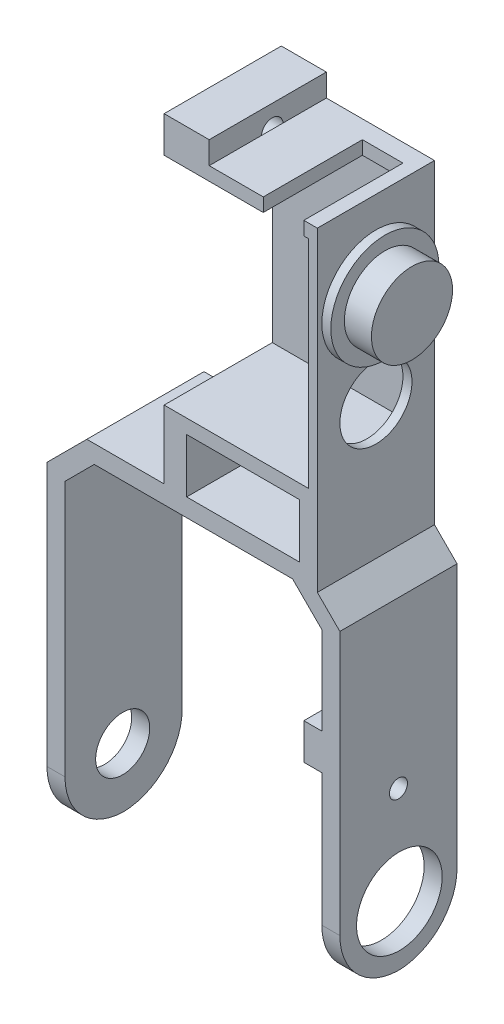
SolidWorks part; units mm, degrees
material "Plain Carbon Steel"
ref_plane "Front Plane" through (0, 0, 0) normal (0, 0, 1) x (1, 0, 0)
ref_plane "Top Plane" through (0, 0, 0) normal (0, 1, 0) x (1, 0, 0)
ref_plane "Right Plane" through (0, 0, 0) normal (1, 0, 0) x (0, 0, -1)
sketch "Sketch1" plane through (0, 0, 0) normal (0, 0, 1) x (1, 0, 0)
  line L0 (0, 20.5639) -> (0, -27.6744) construction
  line L1 (-59.1421, 0) -> (59.1421, 0)
  line L2 (59.1421, 0) -> (81.25, -22.1079)
  line L3 (81.25, -22.1079) -> (81.25, -201.25)
  line L4 (81.25, -201.25) -> (71.25, -201.25)
  line L5 (71.25, -201.25) -> (71.25, -26.25)
  line L6 (71.25, -26.25) -> (55, -10)
  line L8 (-59.1421, 0) -> (-81.25, -22.1079)
  line L9 (-81.25, -22.1079) -> (-81.25, -201.25)
  line L10 (-81.25, -201.25) -> (-71.25, -201.25)
  line L12 (55, -10) -> (-55, -10)
  line L13 (-55, -10) -> (-71.25, -26.25)
  line L14 (-71.25, -26.25) -> (-71.25, -201.25)
  point P6 (0, 0)
  point P19 (-63.125, -18.125)
  dimension "D1" = 175
  dimension "D2" = 71.25
  dimension "D3" = 10
  dimension "D4" = 10
  dimension "D5" = 10
  dimension "D6" = 135
  dimension "D7" = 55
extrude "Boss-Extrude1" add sketch "Sketch1" along normal blind 65
sketch "Sketch2" plane through (0, 0, 0) normal (0, 0, 1) x (1, 0, 0)
  line L0 (68.75, -9.6079) -> (68.75, 165.3921)
  line L1 (81.25, -22.1079) -> (59.1421, 0) construction
  line L2 (68.75, 165.3921) -> (8.75, 165.3921)
  line L3 (8.75, 165.3921) -> (8.75, 177.8921)
  line L4 (8.75, 177.8921) -> (-16.25, 177.8921)
  line L5 (-16.25, 177.8921) -> (-16.25, 0)
  line L6 (59.1421, 0) -> (-59.1421, 0) construction
  line L7 (-16.25, 0) -> (59.1421, 0)
  line L8 (59.1421, 0) -> (68.75, -9.6079)
  dimension "D1" = 25
  dimension "D2" = 12.5
  dimension "D3" = 60
  dimension "D4" = 12.5
  dimension "D5" = 175
extrude "Boss-Extrude2" add sketch "Sketch2" along normal up to surface (65 mm away) up to face at (0, -76.8096, 65)
sketch "Sketch3" plane through (0, 0, 65) normal (0, 0, 1) x (1, 0, 0)
  line L0 (-55, -10) -> (55, -10) construction
  line L1 (-3.75, 30) -> (58.75, 30)
  line L2 (-3.75, 30) -> (-3.75, 0)
  line L3 (-3.75, 0) -> (58.75, 0)
  line L4 (58.75, 30) -> (58.75, 0)
  line L5 (68.75, -9.6079) -> (68.75, 165.3921) construction
  line L6 (-16.25, 177.8921) -> (-16.25, 0) construction
  dimension "D1" = 30
  dimension "D2" = 10
  dimension "D3" = 10
  dimension "D4" = 12.5
extrude "Cut-Extrude1" cut sketch "Sketch3" against normal up to surface (65 mm away) up to face at (3.7269, -14.3974, 0)
sketch "Sketch5" plane through (0, 0, 65) normal (0, 0, 1) x (1, 0, 0)
  line L0 (-16.25, 177.8921) -> (-16.25, 0) construction
  line L1 (-16.25, 157.8921) -> (63.75, 157.8921)
  line L2 (-16.25, 157.8921) -> (-16.25, 37.8921)
  line L3 (-16.25, 37.8921) -> (63.75, 37.8921)
  line L4 (63.75, 157.8921) -> (63.75, 37.8921)
  line L5 (68.75, -9.6079) -> (68.75, 165.3921) construction
  dimension "D1" = 120
  dimension "D2" = 5
  dimension "D3" = 7.5
extrude "Cut-Extrude2" cut sketch "Sketch5" against normal blind 60
sketch "Sketch6" plane through (-16.25, 0, 0) normal (-1, 0, 0) x (0, 0, 1)
  line L0 (5, 157.8921) -> (65, 157.8921) construction
  line L1 (0, 177.8921) -> (0, 0) construction
  line L2 (118.6489, 97.4171) -> (-88.9213, 97.4171) construction
  circle A0 centre (30, 164.8921) radius 6
  circle A1 centre (30, 29.9421) radius 6
  dimension "D1" = 12
  dimension "D2" = 7
  dimension "D3" = 30
  dimension "D4" = 134.95
extrude "Cut-Extrude3" cut sketch "Sketch6" against normal blind 25
fillet "Fillet1" radius 33 4 edges at (76.25, -201.25, 65) (76.25, -201.25, 0) (-76.25, -201.25, 0) (-76.25, -201.25, 65)
sketch "Sketch7" plane through (-81.25, 0, 0) normal (-1, 0, 0) x (0, 0, 1)
  circle A0 centre (33, -168.25) radius 15
  dimension "D1" = 30
extrude "Cut-Extrude4" cut sketch "Sketch7" against normal up to surface (10 mm away) up to face at (-71.25, -120.7128, 32.5)
sketch "Sketch8" plane through (81.25, 0, 0) normal (1, 0, 0) x (0, 0, -1)
  circle A0 centre (-32, -168.25) radius 23.75
  dimension "D1" = 47.5
extrude "Cut-Extrude5" cut sketch "Sketch8" against normal up to surface (10 mm away) up to face at (71.25, -120.7128, 32.5)
sketch "Sketch10" plane through (0, 165.3921, 0) normal (0, 1, 0) x (1, 0, 0)
  line L0 (68.75, -65) -> (8.75, -65) construction
  line L1 (38.75, -65) -> (61.25, -65)
  line L2 (38.75, -65) -> (38.75, -10)
  line L3 (38.75, -10) -> (61.25, -10)
  line L4 (61.25, -65) -> (61.25, -10)
  line L5 (68.75, -65) -> (68.75, 0) construction
  dimension "D1" = 55
  dimension "D2" = 7.5
extrude "Cut-Extrude7" cut sketch "Sketch10" against normal blind 25
sketch "Sketch11" plane through (68.75, 0, 0) normal (1, 0, 0) x (0, 0, -1)
  line L0 (0, -9.6079) -> (0, 165.3921) construction
  circle A0 centre (-32.5, 65.3921) radius 20
  dimension "D1" = 40
  dimension "D3" = 32.5
  dimension "D2" = 100
extrude "Cut-Extrude8" cut sketch "Sketch11" against normal up to surface (5 mm away) up to face at (63.75, 97.8921, 35)
sketch "Sketch12" plane through (68.75, 0, 0) normal (1, 0, 0) x (0, 0, -1)
  line L1 (-65, 165.3921) -> (0, 165.3921) construction
  line L2 (0, -9.6079) -> (0, 165.3921) construction
  circle A1 centre (-32.5, 118.286) radius 30
  dimension "D1" = 60
  dimension "D3" = 32.5
  dimension "D2" = 47.1061
extrude "Boss-Extrude3" add sketch "Sketch12" along normal blind 5
sketch "Sketch13" plane through (73.75, 0, 0) normal (1, 0, 0) x (0, 0, -1)
  circle A0 centre (-32.5, 118.286) radius 22.5
  dimension "D1" = 45
extrude "Boss-Extrude4" add sketch "Sketch13" along normal blind 15
sketch "Sketch14" plane through (0, 0, 0) normal (0, 0, 1) x (1, 0, 0)
  line L0 (71.25, -26.25) -> (71.25, -168.25) construction
  line L1 (71.25, -75) -> (61.25, -75)
  line L2 (71.25, -75) -> (71.25, -95)
  line L3 (71.25, -95) -> (61.25, -95)
  line L4 (61.25, -75) -> (61.25, -95)
  line L5 (-55, -10) -> (55, -10) construction
  point P6 (61.25, -85)
  point P9 (0, -10)
  dimension "D1" = 20
  dimension "D2" = 10
  dimension "D3" = 75
extrude "Boss-Extrude5" add sketch "Sketch14" along normal up to surface (65 mm away) up to face at (15.5715, -4.0511, 65)
sketch "Sketch15" plane through (81.25, 0, 0) normal (1, 0, 0) x (0, 0, -1)
  circle A0 centre (-32.5, -113.83) radius 5
  circle A3 centre (-32, -168.25) radius 23.75 construction
  dimension "D1" = 10
  dimension "D2" = 54.42
extrude "Cut-Extrude9" cut sketch "Sketch15" against normal up to surface (10 mm away) up to face at (71.25, -168.25, 8.25)
